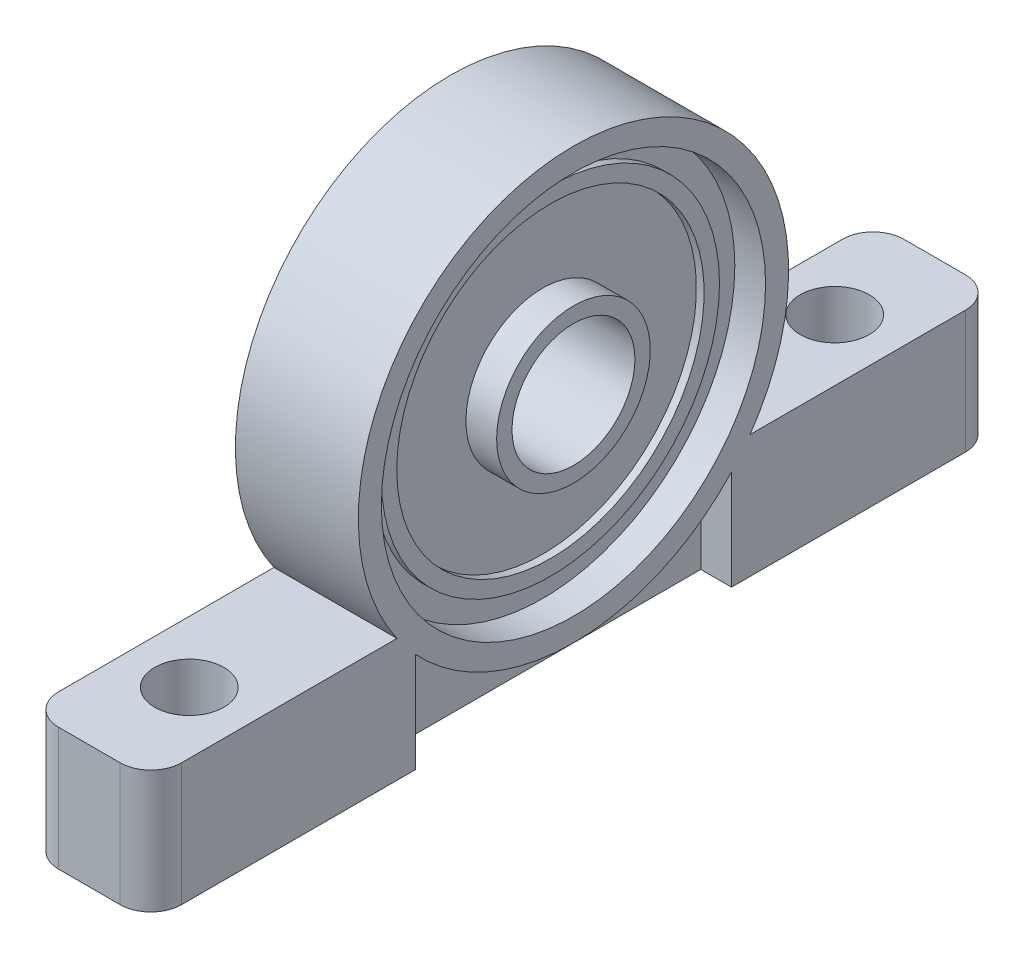
SolidWorks part; units mm, degrees
ref_plane "前视基准面" through (0, 0, 0) normal (0, 0, 1) x (1, 0, 0)
ref_plane "上视基准面" through (0, 0, 0) normal (0, 1, 0) x (1, 0, 0)
ref_plane "右视基准面" through (0, 0, 0) normal (1, 0, 0) x (0, 0, -1)
other "Configuration Table"
sketch "草图1" plane through (0, 0, 0) normal (1, 0, 0) x (0, 0, -1)
  line L0 (13.5301, 8.087) -> (29.541, 8.087)
  line L1 (-25.459, 8.087) -> (-9.4482, 8.087)
  line L2 (-25.459, 8.087) -> (-25.459, 0.087)
  line L3 (-25.459, 0.087) -> (29.541, 0.087)
  line L4 (29.541, 8.087) -> (29.541, 0.087)
  circle A0 centre (2.041, 16.087) radius 4
  arc A1 (13.5301, 8.087) -> (-9.4482, 8.087) centre (2.041, 16.087) ccw
  dimension "D6" = 16
  dimension "D7" = 8
  dimension "D8" = 27.5
  dimension "D1" = 55
  dimension "D2" = 8
extrude "凸台-拉伸1" add sketch "草图1" along normal blind 8
sketch "草图2" plane through (0, 0, 0) normal (-1, 0, 0) x (0, 0, 1)
  circle A0 centre (-2.041, 16.087) radius 4
  circle A1 centre (-2.041, 16.087) radius 5
extrude "凸台-拉伸2" add sketch "草图2" along normal blind 4
sketch "草图3" plane through (0, 0, 0) normal (-1, 0, 0) x (0, 0, 1)
  circle A0 centre (-2.041, 16.087) radius 5
  circle A1 centre (-2.041, 16.087) radius 10.0005
extrude "切除-拉伸1" cut sketch "草图3" against normal blind 2
sketch "草图4" plane through (0, 0, 0) normal (-1, 0, 0) x (0, 0, 1)
  circle A0 centre (-2.041, 16.087) radius 11
  circle A1 centre (-2.041, 16.087) radius 10.0005
extrude "切除-拉伸2" cut sketch "草图4" against normal blind 1.5
sketch "草图5" plane through (0, 0, 0) normal (-1, 0, 0) x (0, 0, 1)
  circle A0 centre (-2.041, 16.087) radius 11
  circle A1 centre (-2.041, 16.087) radius 12.5
extrude "切除-拉伸3" cut sketch "草图5" against normal blind 2
sketch "草图6" plane through (0, 0, 0) normal (-1, 0, 0) x (0, 0, 1)
  line L2 (25.459, 0.087) -> (-29.541, 0.087) construction
  line L4 (-12.3244, 6.587) -> (-12.3244, 0.087)
  line L5 (8.2425, 6.587) -> (8.2425, 0.087)
  line L6 (-12.3244, 0.087) -> (8.2425, 0.087)
  arc A0 (-12.3244, 6.587) -> (8.2425, 6.587) centre (-2.041, 16.087) ccw
  dimension "D1" = 10.2835
  dimension "D3" = 6.5
  dimension "D4" = 6.5
extrude "切除-拉伸4" cut sketch "草图6" against normal blind 2
fillet "圆角1" radius 2 4 edges at (0, 4.087, -29.541) (8, 4.087, -29.541) (8, 4.087, 25.459) (0, 4.087, 25.459)
fillet "圆角2" radius 1 2 edges at (0, 3.337, 8.2425) (0, 3.337, -12.3244)
ref_plane "基准面1" through (4, 0, 0) normal (-1, 0, 0) x (0, 0, 1)
mirror "镜向1" about plane through (4, 0, 0) normal (-1, 0, 0) of "切除-拉伸1"
mirror "镜向2" about plane through (4, 0, 0) normal (-1, 0, 0) of "切除-拉伸2"
mirror "镜向3" about plane through (4, 0, 0) normal (-1, 0, 0) of "切除-拉伸4", "切除-拉伸3"
sketch "草图9" plane through (0, 0, 0) normal (0, 1, 0) x (1, 0, 0)
  line L0 (2, 7.041) -> (-4, 7.041) construction
  line L1 (-4, 7.041) -> (-4, -2.959) construction
  circle A0 centre (-2, 2.041) radius 0.75
  dimension "D1" = 5
  dimension "D2" = 2
  dimension "D3" = 1.5
extrude "切除-拉伸5" cut sketch "草图9" along normal blind 18
ref_plane "基准面2" through (0, 0, -2.041) normal (0, 0, -1) x (-1, 0, 0)
sketch "草图11" plane through (0, 8.087, 0) normal (0, 1, 0) x (1, 0, 0)
  line L0 (4, 16.5) -> (4, -16.5) construction
  line L1 (6, 29.541) -> (2, 29.541) construction
  circle A0 centre (4, 23.041) radius 2.25
  circle A1 centre (4, -18.959) radius 2.25
  dimension "D1" = 4.5
  dimension "D2" = 4.5
  dimension "D3" = 42
  dimension "D4" = 6.5
extrude "切除-拉伸6" cut sketch "草图11" against normal blind 10
